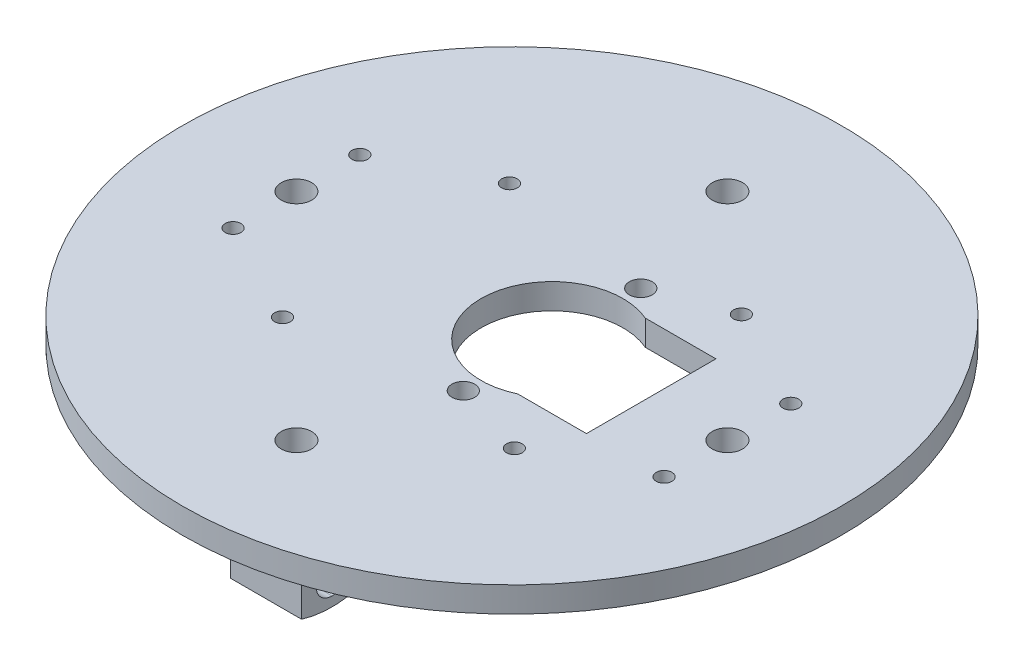
SolidWorks part; units mm, degrees
ref_plane "Front Plane" through (0, 0, 0) normal (0, 0, 1) x (1, 0, 0)
ref_plane "Top Plane" through (0, 0, 0) normal (0, 1, 0) x (1, 0, 0)
ref_plane "Right Plane" through (0, 0, 0) normal (1, 0, 0) x (0, 0, -1)
sketch "Sketch1" plane through (0, 0, 0) normal (0, 1, 0) x (1, 0, 0)
  line L0 (65, 5) -> (65, -5) construction
  line L1 (-5, 65) -> (5, 65) construction
  line L2 (-5, 65) -> (-5, 20) construction
  line L3 (-5, 20) -> (5, 20) construction
  line L4 (5, 65) -> (5, 20) construction
  line L5 (-5, 65) -> (5, 20) construction
  line L6 (-5, 20) -> (5, 65) construction
  line L7 (65, 5) -> (20, 5) construction
  line L8 (20, 5) -> (20, -5) construction
  line L9 (65, -5) -> (20, -5) construction
  line L10 (65, 5) -> (20, -5) construction
  line L11 (20, 5) -> (65, -5) construction
  line L12 (5, -65) -> (-5, -65) construction
  line L13 (5, -65) -> (5, -20) construction
  line L14 (5, -20) -> (-5, -20) construction
  line L15 (-5, -65) -> (-5, -20) construction
  line L16 (5, -65) -> (-5, -20) construction
  line L17 (5, -20) -> (-5, -65) construction
  line L18 (-65, -5) -> (-65, 5) construction
  line L19 (-65, -5) -> (-20, -5) construction
  line L20 (-20, -5) -> (-20, 5) construction
  line L21 (-65, 5) -> (-20, 5) construction
  line L22 (-65, -5) -> (-20, 5) construction
  line L23 (-20, -5) -> (-65, 5) construction
  line L24 (0, -55) -> (0, 55) construction
  circle A0 centre (0, 0) radius 65
  circle A1 centre (0, 0) radius 5
  circle A2 centre (0, 42.5) radius 3
  circle A3 centre (42.5, 0) radius 3
  circle A4 centre (0, -42.5) radius 3
  circle A5 centre (-42.5, 0) radius 3
  circle A6 centre (-42.5, -12.5) radius 1.55
  circle A7 centre (-42.5, 12.5) radius 1.55
  circle A8 centre (42.5, -12.5) radius 1.55
  circle A9 centre (42.5, 12.5) radius 1.55
  circle A10 centre (-22.8679, 22.3843) radius 1.55
  circle A11 centre (22.3843, 22.8679) radius 1.55
  circle A12 centre (22.8679, -22.3843) radius 1.55
  circle A13 centre (-22.3843, -22.8679) radius 1.55
  point P3 (0, 42.5)
  point P11 (42.5, 0)
  point P16 (0, -42.5)
  point P21 (-42.5, 0)
  point P26 (0, 0)
  point P36 (0, 0)
  point P56 (0, 0)
  dimension "D1" = 130
  dimension "D5" = 10
  dimension "D6" = 6
  dimension "D8" = 3.1
  dimension "D12" = 32
  dimension "D13" = 3.1
  dimension "D2" = 10
  dimension "D3" = 45
  dimension "D9" = 25
  dimension "D10" = 12.5
  dimension "D4" = 4
  dimension "D7" = 4
  dimension "D11" = 4
extrude "Boss-Extrude1" add sketch "Sketch1" along normal blind 5
sketch "Sketch2" plane through (0, 0, 0) normal (0, -1, 0) x (-1, 0, 0)
  circle A3 centre (-7.9995, -0.0923) radius 14
  circle A5 centre (-2.1282, -3.2886) radius 0.0329 construction
  circle A6 centre (0, 0) radius 4.5 construction
  circle A12 centre (0, 0) radius 5 construction
  dimension "D1" = 8
  dimension "D2" = 28
extrude "Cut-Extrude2" cut sketch "Sketch2" against normal blind 10
sketch "Sketch3" plane through (0, 0, 0) normal (0, -1, 0) x (-1, 0, 0)
  line L1 (-10.1618, -12.767) -> (-27.4636, -12.767)
  line L2 (-10.1618, -12.767) -> (-10.1618, 12.767)
  line L3 (-10.1618, 12.767) -> (-27.4636, 12.767)
  line L4 (-27.4636, -12.767) -> (-27.4636, 12.767)
  line L5 (-10.1618, -12.767) -> (-27.4636, 12.767) construction
  line L6 (-10.1618, 12.767) -> (-27.4636, -12.767) construction
  circle A0 centre (-7.9995, -17.5923) radius 2.25
  circle A1 centre (-7.9995, 17.4077) radius 2.25
  point P6 (-18.8127, 0)
extrude "Cut-Extrude3" cut sketch "Sketch3" against normal blind 10
sketch "Sketch4" plane through (0, 5, 0) normal (0, 1, 0) x (1, 0, 0)
  line L2 (-7, 42.5) -> (-7, 22.5)
  line L3 (-7, 22.5) -> (7, 22.5)
  line L4 (7, 42.5) -> (7, 22.5)
  line L7 (-7, 42.5) -> (-7, 48.5)
  line L8 (-7, 48.5) -> (7, 48.5)
  line L9 (7, 42.5) -> (7, 48.5)
  circle A0 centre (0, 42.5) radius 3
  point P6 (0, 48.5)
  dimension "D1" = 14
  dimension "D2" = 20
  dimension "D3" = 6
extrude "Boss-Extrude2" add sketch "Sketch4" against normal blind 22.5 from surface starting at face at (7.9995, 0, 15.3423)
sketch "Sketch6" plane through (0, -22.5, 0) normal (0, -1, 0) x (-1, 0, 0)
  line L0 (-7, 22.5) -> (7, 22.5) construction
  line L1 (-3, 42.5) -> (3, 42.5)
  line L2 (-3, 42.5) -> (-3, 22.5)
  line L3 (-3, 22.5) -> (3, 22.5)
  line L4 (3, 42.5) -> (3, 22.5)
  circle A0 centre (0, 42.5) radius 3 construction
extrude "Cut-Extrude4" cut sketch "Sketch6" against normal blind 22.5
sketch "Sketch7" plane through (7, 0, 0) normal (1, 0, 0) x (0, 0, -1)
  line L5 (42.5, 0) -> (42.5, -22.5) construction
  line L6 (22.5, 0) -> (48.5, 0) construction
  line L7 (12.396, 0) -> (22.5, 0)
  line L8 (48.5, -29.5) -> (48.5, -19.0788)
  line L9 (48.5, -22.5) -> (48.5, 0) construction
  arc A7 (42.5, -18.1) -> (42.5, -11.9) centre (42.5, -15) ccw
  arc A8 (30.4153, -8.886) -> (45.5834, -14.6797) centre (42.5, 0) ccw construction
  arc A9 (34.5667, -8.8697) -> (42.5, -11.9) centre (42.5, 0) ccw
  arc A10 (30.4333, -13.4909) -> (42.5, -18.1) centre (42.5, 0) ccw
  arc A11 (34.5667, -8.8697) -> (30.4333, -13.4909) centre (32.5, -11.1803) ccw
  arc A12 (22.5, 0) -> (48.5, -19.0788) centre (42.5, 0) ccw
  arc A13 (12.396, 0) -> (48.5, -29.5) centre (42.5, 0) ccw
  dimension "D2" = 15
  dimension "D1" = 6.2
  dimension "D3" = 10
extrude "Cut-Extrude5" cut sketch "Sketch7" against normal up to surface (14 mm away) up to face at (-7, -11.25, -35.5)
mirror "Mirror1" about plane through (0, 0, 0) normal (0, 0, 1) of "Cut-Extrude4", "Cut-Extrude5", "Boss-Extrude2"
